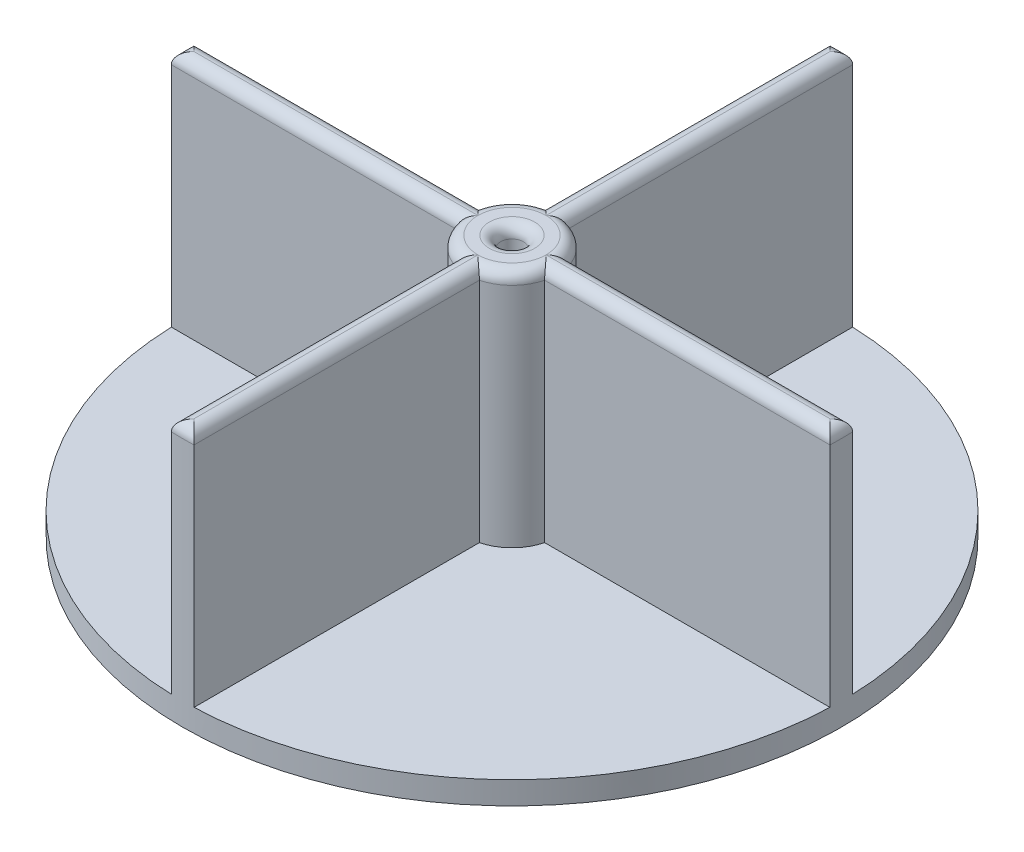
SolidWorks part; units mm, degrees
ref_plane "Front Plane" through (0, 0, 0) normal (0, 0, 1) x (1, 0, 0)
ref_plane "Top Plane" through (0, 0, 0) normal (0, 1, 0) x (1, 0, 0)
ref_plane "Right Plane" through (0, 0, 0) normal (1, 0, 0) x (0, 0, -1)
sketch "Sketch1" plane through (0, 0, 0) normal (0, 1, 0) x (1, 0, 0)
  circle A0 centre (0, 0) radius 23.2
  dimension "D1" = 46.4
extrude "Boss-Extrude1" add sketch "Sketch1" along normal blind 1.6
sketch "Sketch2" plane through (0, 1.6, 0) normal (0, 1, 0) x (1, 0, 0)
  line L0 (0, 0) -> (-23.2, 0) construction
  line L1 (-3.0984, 0.8) -> (-23.1862, 0.8)
  line L2 (-3.0984, -0.8) -> (-23.1862, -0.8)
  line L3 (-0.8, 3.0984) -> (-0.8, 23.1862)
  line L4 (0.8, 3.0984) -> (0.8, 23.1862)
  line L5 (3.0984, 0.8) -> (23.1862, 0.8)
  line L6 (3.0984, -0.8) -> (23.1862, -0.8)
  line L7 (0.8, -3.0984) -> (0.8, -23.1862)
  line L8 (-0.8, -3.0984) -> (-0.8, -23.1862)
  arc A0 (-3.0984, -0.8) -> (-0.8, -3.0984) centre (0, 0) ccw
  circle A2 centre (0, 0) radius 23.2 construction
  arc A3 (-23.1862, 0.8) -> (-23.1862, -0.8) centre (0, 0) ccw
  arc A4 (0.8, 23.1862) -> (-0.8, 23.1862) centre (0, 0) ccw
  arc A5 (23.1862, -0.8) -> (23.1862, 0.8) centre (0, 0) ccw
  arc A6 (-0.8, -23.1862) -> (0.8, -23.1862) centre (0, 0) ccw
  arc A7 (-0.8, 3.0984) -> (-3.0984, 0.8) centre (0, 0) ccw
  arc A8 (3.0984, 0.8) -> (0.8, 3.0984) centre (0, 0) ccw
  arc A9 (0.8, -3.0984) -> (3.0984, -0.8) centre (0, 0) ccw
  point P25 (0, 0)
  dimension "D1" = 6.4
  dimension "D2" = 0.8
extrude "Boss-Extrude2" add sketch "Sketch2" along normal blind 16.8
sketch "Sketch3" plane through (0, 0, 0) normal (0, -1, 0) x (-1, 0, 0)
  circle A0 centre (0, 0) radius 0.8
  dimension "D1" = 1.6
extrude "Cut-Extrude1" cut sketch "Sketch3" against normal through all
fillet "Fillet2" radius 0.8 17 edges at (-13.1423, 18.4, -0.8) (-2.2627, 18.4, -2.2627) (-0.8, 18.4, -13.1423) (0, 18.4, -23.2) (0.8, 18.4, -13.1423) (2.2627, 18.4, -2.2627) (13.1423, 18.4, -0.8) (23.2, 18.4, 0) (13.1423, 18.4, 0.8) (2.2627, 18.4, 2.2627) (0.8, 18.4, 13.1423) (0, 18.4, 23.2) (-0.8, 18.4, 13.1423) (-2.2627, 18.4, 2.2627) (-13.1423, 18.4, 0.8) (-23.2, 18.4, 0) (0, 18.4, -0.8)
equation "\"D1@Sketch1\"=0.8*58"
equation "\"D1@Boss-Extrude1\"=0.8*2"
equation "\"D1@Boss-Extrude2\"=0.8*21"
equation "\"D1@Sketch3\"=0.8*2"
